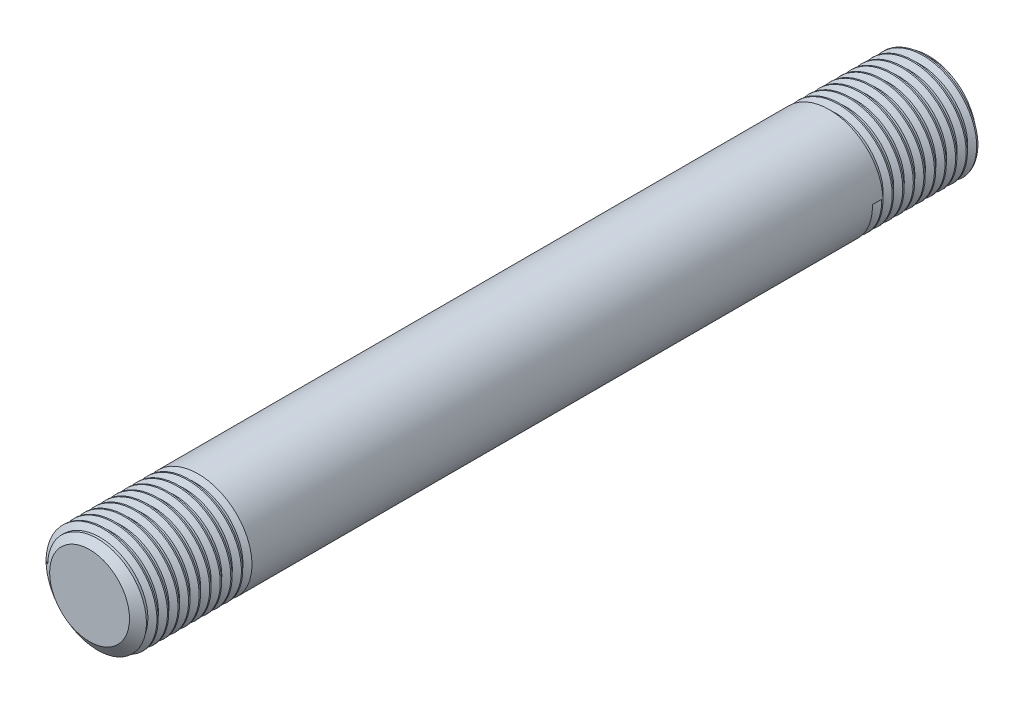
SolidWorks part; units mm, degrees
ref_plane "Спереди" through (0, 0, 0) normal (0, 0, 1) x (1, 0, 0)
ref_plane "Сверху" through (0, 0, 0) normal (0, 1, 0) x (1, 0, 0)
ref_plane "Справа" through (0, 0, 0) normal (1, 0, 0) x (0, 0, -1)
sketch "Эскиз1" plane through (0, 0, 0) normal (0, 0, 1) x (1, 0, 0)
  circle A0 centre (0, 0) radius 10
  dimension "D1" = 20
extrude "Бобышка-Вытянуть1" add sketch "Эскиз1" along normal mid plane 160
thread "Резьба1" pitch 2 method cut profile "Профиль резьбы1" start angle 0, offset 0, length 20, pitch 2, diameter 20
ref_plane "Плоскость4" through (10, 0, -80) normal (0, -1, 0) x (1, 0, 0)
sketch "Профиль резьбы1" plane through (10, 0, -80) normal (0, -1, 0) x (1, 0, 0)
  line L0 (0, 0) -> (0, 2) construction
  line L11 (0, 0) -> (0, 1.75)
  line L12 (0, 1.75) -> (-1.0825, 1.125)
  line L13 (-1.0825, 1.125) -> (-1.0825, 0.625)
  line L15 (-1.0825, 0.625) -> (0, 0)
  line L17 (-1.0825, 0.875) -> (0, 0.875) construction
  point P2 (0, 0)
  dimension "Pitch" = 2
  dimension "Profile_Angle" = 60
  dimension "Profile_Land" = 0.5
  dimension "Profile_Height" = 1.0825
thread "Резьба2" pitch 2 method cut profile "Профиль резьбы2" start angle 0, offset 0, length 20, pitch 2, diameter 20
ref_plane "Плоскость5" through (-10, 0, 80) normal (0, -1, 0) x (-1, 0, 0)
sketch "Профиль резьбы2" plane through (-10, 0, 80) normal (0, -1, 0) x (-1, 0, 0)
  line L0 (0, 0) -> (0, 2) construction
  line L11 (0, 0) -> (0, 1.75)
  line L12 (0, 1.75) -> (-1.0825, 1.125)
  line L13 (-1.0825, 1.125) -> (-1.0825, 0.625)
  line L15 (-1.0825, 0.625) -> (0, 0)
  line L17 (-1.0825, 0.875) -> (0, 0.875) construction
  point P2 (0, 0)
  dimension "Pitch" = 2
  dimension "Profile_Angle" = 60
  dimension "Profile_Land" = 0.5
  dimension "Profile_Height" = 1.0825
sketch "Эскиз8" plane through (0, 0, 0) normal (0, 1, 0) x (1, 0, 0)
  line L1 (10, 80) -> (10, 78.25)
  line L2 (10, 78.25) -> (7.5633, 80)
  line L3 (7.5633, 80) -> (10, 80)
  line L4 (-10, -78.25) -> (-10, -80)
  line L5 (-10, -78.25) -> (-7.5633, -80)
  line L6 (-10, -80) -> (10, -80) construction
  line L7 (-7.5633, -80) -> (-10, -80)
  line L8 (10, 80) -> (-10, 80) construction
  line L9 (0, -1000) -> (0, 49000) construction
  dimension "D1" = 3
  dimension "D2" = 3
revolve "Вырез-Повернуть1" cut sketch "Эскиз8" angle 360 about L9
